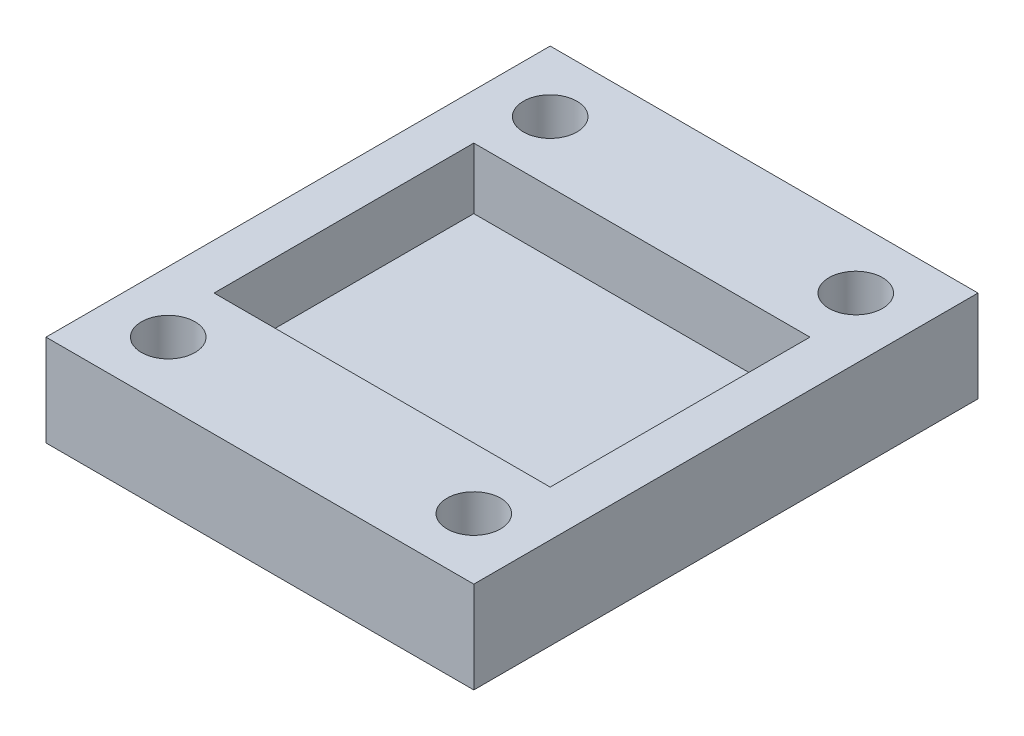
SolidWorks part; units mm, degrees
ref_plane "Front Plane" through (0, 0, 0) normal (0, 0, 1) x (1, 0, 0)
ref_plane "Top Plane" through (0, 0, 0) normal (0, 1, 0) x (1, 0, 0)
ref_plane "Right Plane" through (0, 0, 0) normal (1, 0, 0) x (0, 0, -1)
sketch "Sketch1" plane through (0, 0, 0) normal (0, 1, 0) x (1, 0, 0)
  line L0 (-3, -8) -> (-3, 25)
  line L1 (0, 0) -> (22, 0)
  line L2 (0, 0) -> (0, 17)
  line L3 (0, 17) -> (22, 17)
  line L4 (22, 0) -> (22, 17)
  line L5 (25, 25) -> (-3, 25)
  line L6 (-3, -8) -> (25, -8)
  line L7 (25, -8) -> (25, 25)
  line L8 (-3, -8) -> (5, 0) construction
  line L9 (0, 8.5) -> (22, 8.5) construction
  line L10 (11, 17) -> (11, 0) construction
  circle A0 centre (21, -4) radius 1.75
  circle A1 centre (1, -4) radius 1.75
  circle A2 centre (21, 21) radius 1.75
  circle A3 centre (1, 21) radius 1.75
  dimension "3.5" = 3.5
  dimension "D1" = 17
  dimension "D2" = 22
  dimension "D3" = 3
  dimension "D4" = 3
  dimension "D5" = 8
  dimension "D6" = 8
  dimension "D7" = 45
extrude "Boss-Extrude1" add sketch "Sketch1" along normal blind 2 contours L1 L4 L3 L2 region at (11, 0, -8.5)
extrude "Boss-Extrude2" add sketch "Sketch1<3>" along normal blind 6
sketch "Sketch1<3>" plane through (0, 0, 0) normal (0, 1, 0) x (1, 0, 0) same geometry as "Sketch1"
